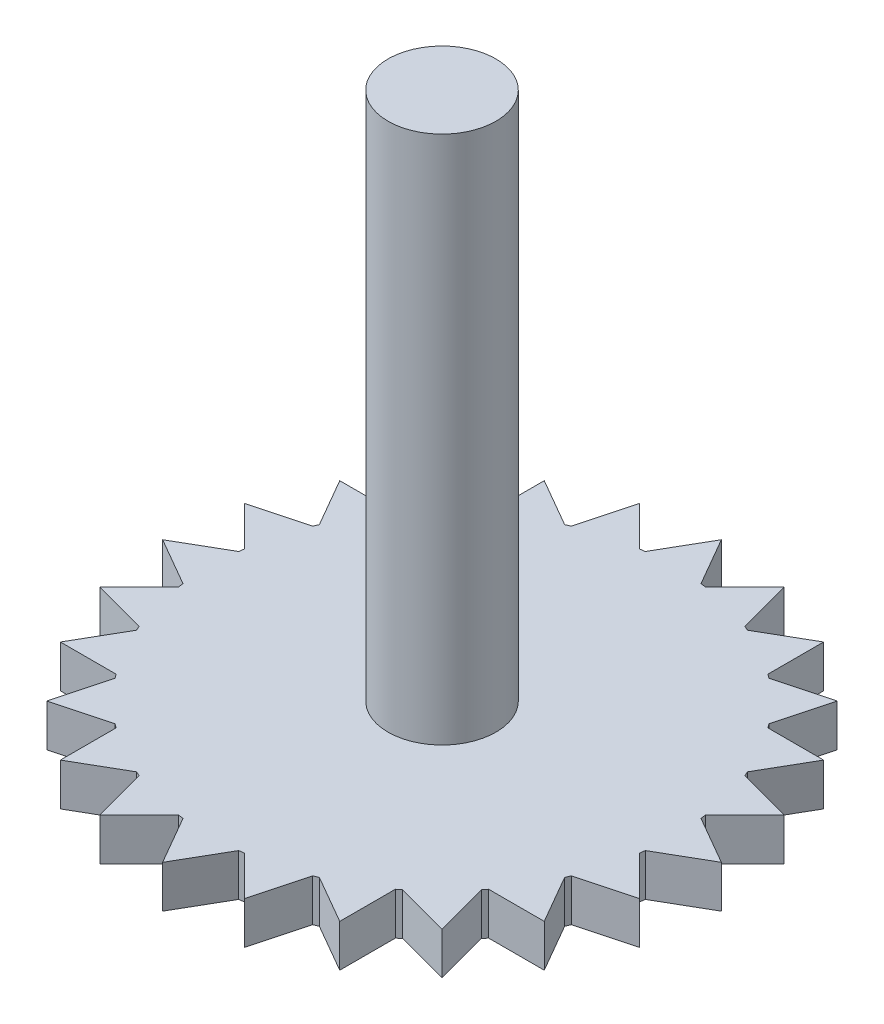
SolidWorks part; units mm, degrees
ref_plane "Front Plane" through (0, 0, 0) normal (0, 0, 1) x (1, 0, 0)
ref_plane "Top Plane" through (0, 0, 0) normal (0, 1, 0) x (1, 0, 0)
ref_plane "Right Plane" through (0, 0, 0) normal (1, 0, 0) x (0, 0, -1)
sketch "Sketch1" plane through (0, 0, 0) normal (0, 1, 0) x (1, 0, 0)
  circle A0 centre (0, 0) radius 13.97
  dimension "D1" = 27.94
extrude "Boss-Extrude1" add sketch "Sketch1" along normal blind 2.54
sketch "Sketch2" plane through (0, 2.54, 0) normal (0, 1, 0) x (1, 0, 0)
  line L0 (0, 0) -> (0, -16.764)
  line L1 (0, -16.764) -> (3.6473, -10.4467)
  line L2 (0, -16.764) -> (-3.5819, -10.56)
  line L3 (-3.5819, -10.56) -> (3.6473, -10.4467)
  dimension "D1" = 16.764
  dimension "D2" = 30
  dimension "D3" = 30
extrude "Boss-Extrude2" add sketch "Sketch2" against normal blind 2.54 contours L2 L3 L1
ref_axis "Axis1" through (0, 2.667, 0) along (0, -1, 0)
pattern_circular "CirPattern1" count 24 every 15 about axis through (0, 2.667, 0) along (0, -1, 0) of "Boss-Extrude2"
sketch "Sketch3" plane through (0, 2.54, 0) normal (0, 1, 0) x (1, 0, 0)
  circle A0 centre (0, 0) radius 3.2385
  dimension "D1" = 6.477
extrude "Boss-Extrude3" add sketch "Sketch3" along normal blind 31.75 contours A0
